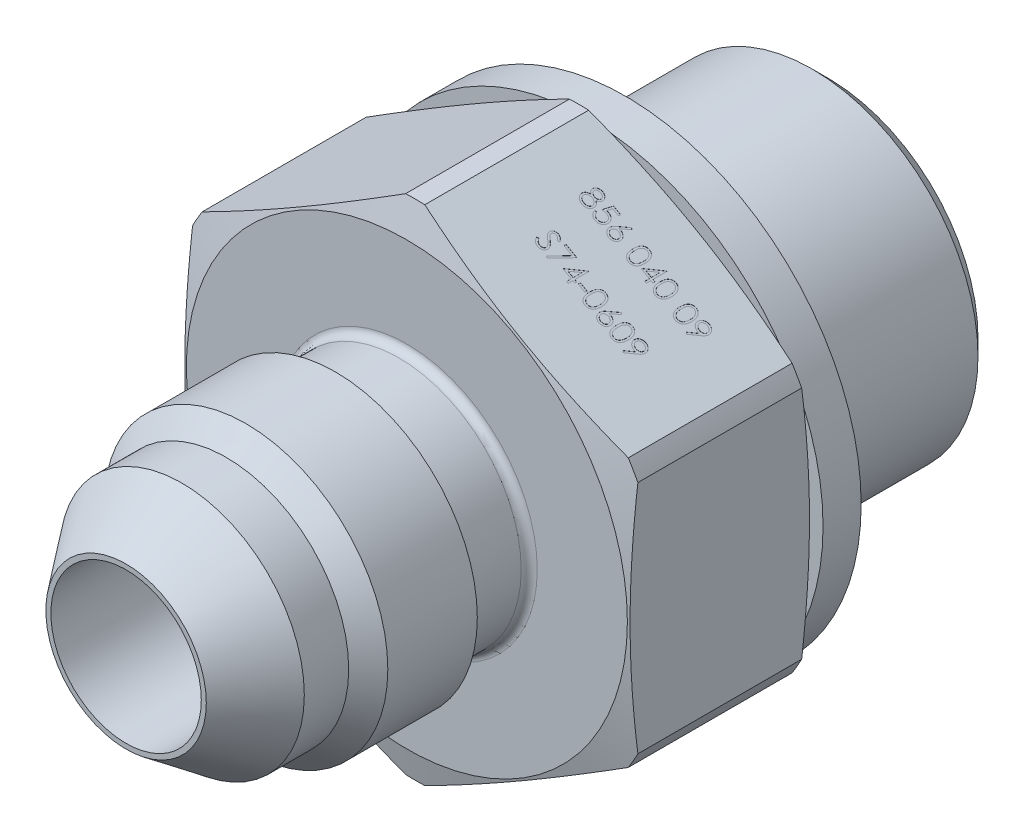
SolidWorks part; units mm, degrees
material "Plain Carbon Steel"
ref_plane "Front Plane" through (0, 0, 0) normal (0, 0, 1) x (1, 0, 0)
ref_plane "Top Plane" through (0, 0, 0) normal (0, 1, 0) x (1, 0, 0)
ref_plane "Right Plane" through (0, 0, 0) normal (1, 0, 0) x (0, 0, -1)
sketch "Sketch1" plane through (0, 0, 0) normal (1, 0, 0) x (0, 0, -1)
  line L0 (0, 0) -> (90.3331, 0) construction
  line L1 (0, 4) -> (2.7868, 6.1)
  line L2 (2.7868, 6.1) -> (5, 6.1)
  line L3 (5, 6.1) -> (5.975, 7.075)
  line L4 (5.975, 7.075) -> (10.4371, 7.075)
  line L6 (11, 6.1) -> (13.6, 6.1)
  line L7 (14, 6.5) -> (14, 10.994)
  line L8 (14.4169, 12.55) -> (22.5831, 12.55)
  line L9 (23, 10.994) -> (23, 7.25)
  line L10 (26.5, 8.275) -> (34.2, 8.275)
  line L11 (35, 7.475) -> (35, 7)
  line L12 (35, 7) -> (31.5359, 5)
  line L13 (19.7489, 3.75) -> (0, 3.75)
  line L14 (0, 3.75) -> (0, 4)
  line L15 (34.2, 8.275) -> (35, 7.475)
  line L16 (14.4169, 12.55) -> (14, 10.994)
  line L17 (22.5831, 12.55) -> (23, 10.994)
  line L18 (19.7489, 3.75) -> (20.5, 5)
  line L19 (20.5, 5) -> (31.5359, 5)
  line L20 (26.5, 8.275) -> (25.475, 7.25)
  line L21 (25.475, 7.25) -> (23, 7.25)
  line L22 (10.4371, 7.075) -> (11, 6.1)
  arc A0 (13.6, 6.1) -> (14, 6.5) centre (13.6, 6.5) ccw
  point P14 (35, 8.275)
  dimension "D28" = 0.4
  dimension "D1" = 25.1
  dimension "D2" = 16.55
  dimension "D3" = 8
  dimension "D4" = 14
  dimension "D5" = 30
  dimension "D6" = 12
  dimension "D7" = 35
  dimension "D8" = 60
  dimension "D9" = 5
  dimension "D10" = 12.2
  dimension "D11" = 14.15
  dimension "D12" = 14
  dimension "D13" = 7.5
  dimension "D14" = 37
  dimension "D15" = 15
  dimension "D16" = 15
  dimension "D18" = 1.556
  dimension "D19" = 10
  dimension "D20" = 14.5
  dimension "D21" = 59
  dimension "D22" = 8.5
  dimension "D23" = 45
  dimension "D24" = 14.5
  dimension "D25" = 45
  dimension "D26" = 3
  dimension "D27" = 12.2
  dimension "D29" = 9
revolve "Revolve1" add sketch "Sketch1" angle 360 about L0
cosmetic thread "Cosmetic Thread1" parameters "D2"=13
cosmetic thread "Cosmetic Thread2" parameters "D2"=15.2
sketch "Sketch2" plane through (0, 0, -14) normal (0, 0, 1) x (1, 0, 0)
  line L1 (0, 12.8172) -> (-11.1, 6.4086)
  line L2 (-11.1, 6.4086) -> (-11.1, -6.4086)
  line L3 (-11.1, -6.4086) -> (0, -12.8172)
  line L4 (0, -12.8172) -> (11.1, -6.4086)
  line L5 (11.1, -6.4086) -> (11.1, 6.4086)
  line L6 (11.1, 6.4086) -> (0, 12.8172)
  circle A0 centre (0, 0) radius 11.1 construction
  dimension "D1" = 22.2
extrude "Extrude2" cut sketch "Sketch2" against normal up to surface (9 mm away) flip side to cut up to face at (10.994, 0, -23)
sketch "Sketch3" plane through (0, 0, -23) normal (0, 0, -1) x (-1, 0, 0)
  circle A0 centre (0, 0) radius 11.75
  circle A1 centre (0, 0) radius 9.6
  dimension "D1" = 23.5
  dimension "D2" = 19.2
extrude "Extrude3" add sketch "Sketch3" along normal blind 1.9 separate body
sketch "Sketch5" plane through (5.55, 9.6129, 0) normal (0.5, 0.866, 0) x (0.866, -0.5, 0)
  line L0 (-5.7258, 19.8095) -> (5.856, 19.8095) construction
  line L1 (5.856, 14.4169) -> (5.856, 22.5831) construction
  text T0 "856 040 09\r\nS74-0609" font "Century Gothic" height 1
extrude "Cut-Extrude1" cut sketch "Sketch5" against normal blind 0.01
sketch "Sketch6" plane through (0, 0, 0) normal (1, 0, 0) x (0, 0, -1)
  line L0 (0, 0) -> (40.5913, 0) construction
  line L1 (24.9, -11.75) -> (24.9, 11.75) construction
  circle A0 centre (24.1, 8.45) radius 1.2
  dimension "D1" = 14.5
  dimension "D2" = 2.4
  dimension "D3" = 0.8
revolve "Revolve2" add sketch "Sketch6" angle 360 about L0
